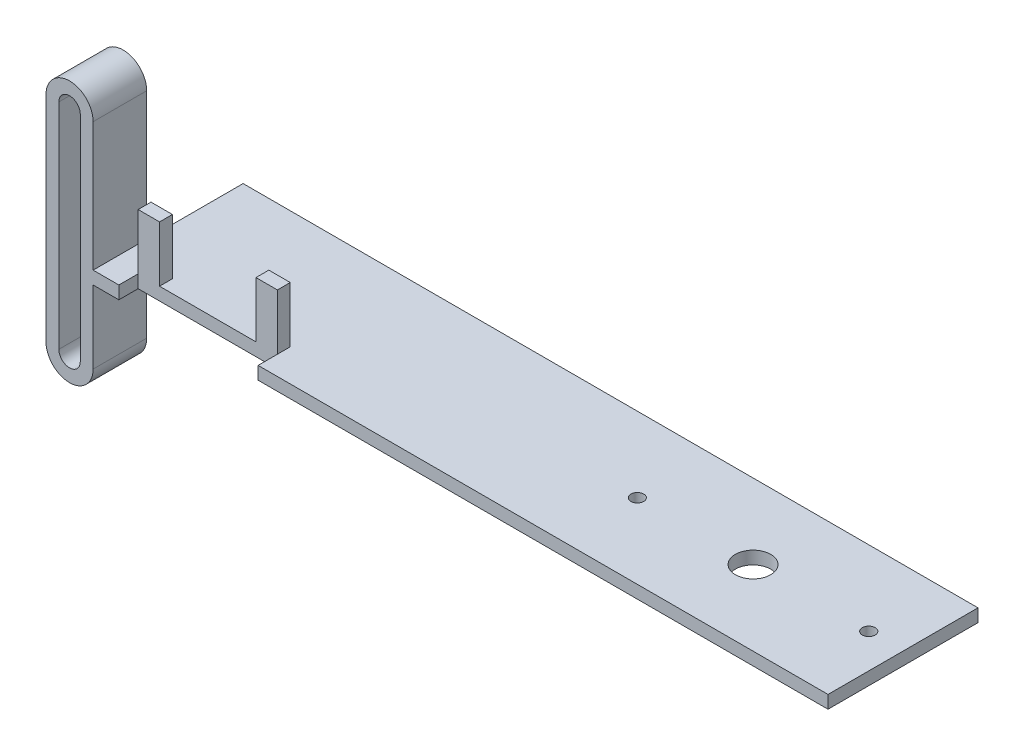
SolidWorks part; units mm, degrees
ref_plane "Front Plane" through (0, 0, 0) normal (0, 0, 1) x (1, 0, 0)
ref_plane "Top Plane" through (0, 0, 0) normal (0, 1, 0) x (1, 0, 0)
ref_plane "Right Plane" through (0, 0, 0) normal (1, 0, 0) x (0, 0, -1)
sketch "Sketch1" plane through (0, 0, 0) normal (0, 1, 0) x (1, 0, 0)
  line L0 (47.5, 13.6856) -> (47.5, -3.2344) construction
  line L1 (-100, 22.5) -> (82.5, 22.5)
  line L2 (-100, 22.5) -> (-100, -12.5)
  line L3 (-100, -12.5) -> (82.5, -12.5)
  line L4 (82.5, 22.5) -> (82.5, -12.5)
  line L6 (12.5, -1) -> (82.5, -1)
  line L7 (12.5, -1) -> (12.5, 11)
  line L8 (12.5, 11) -> (82.5, 11)
  line L9 (82.5, -1) -> (82.5, 11)
  line L10 (12.5, -1) -> (82.5, 11) construction
  line L11 (12.5, 11) -> (82.5, -1) construction
  circle A4 centre (47.5, 5) radius 4.125
  circle A5 centre (74.5, 5) radius 1.5
  circle A6 centre (20.5, 5) radius 1.5
  point P0 (0, 0)
  point P19 (0, 0)
  point P20 (0, 0)
  dimension "D4" = 8.25
  dimension "D5" = 3
  dimension "D1" = 35
  dimension "D2" = 182.5
  dimension "D6" = 8
  dimension "D7" = 70
  dimension "D8" = 12
extrude "Boss-Extrude1" add sketch "Sketch1" along normal blind 3 contours L7 L8 L4 L1 L2 L3 L6 | L8 L7 L6 L4 A4 A5 A6 region at (-17.2674, 0, -5) region at (81.7898, 0, -5)
sketch "Sketch2" plane through (0, 0, 0) normal (0, 0, 1) x (1, 0, 0)
  line L0 (-94.5, 33) -> (-94.5, -17) construction
  line L1 (-92, 33) -> (-92, -17)
  line L2 (-97, 33) -> (-97, -17)
  line L3 (-89, 33) -> (-89, -17)
  line L4 (-100, 33) -> (-100, -17)
  line L7 (-83, 6.4998) -> (-50.5, 6.4998)
  line L8 (-83, 6.4998) -> (-83, -3.3981)
  line L9 (-83, -3.3981) -> (-50.5, -3.3981)
  line L10 (-50.5, 6.4998) -> (-50.5, -3.3981)
  arc A0 (-92, 33) -> (-97, 33) centre (-94.5, 33) ccw
  arc A1 (-97, -17) -> (-92, -17) centre (-94.5, -17) ccw
  arc A2 (-100, -17) -> (-89, -17) centre (-94.5, -17) ccw
  arc A3 (-89, 33) -> (-100, 33) centre (-94.5, 33) ccw
  point P2 (-94.5, 8)
  dimension "D4" = 5.5
  dimension "D1" = 3
  dimension "D2" = 3
  dimension "D3" = 5
  dimension "D5" = 50
  dimension "D6" = 50
  dimension "D7" = 6
  dimension "D8" = 32.5
extrude "Boss-Extrude2" add sketch "Sketch2" along normal up to surface (12.5 mm away) contours L3 A3 L4 A2 A1 L2 A0 L1 region at (-89.6198, 8, 0) up to face at (-8.75, 1.5, 12.5)
extrude "Cut-Extrude1" cut sketch "Sketch2<2>" against normal through all both and the other way through all contours L2 A1 L1 A0 region at (-94.5, 8, 0)
sketch "Sketch2<2>" plane through (0, 0, 0) normal (0, 0, 1) x (1, 0, 0) same geometry as "Sketch2"
extrude "Cut-Extrude2" cut sketch "Sketch2<3>" against normal up to surface (22.5 mm away) contours L3 A3 L4 A2 A1 L2 A0 L1 region at (-89.6198, 8, 0) up to face at (-4.75, 1.5, -22.5)
sketch "Sketch2<3>" plane through (0, 0, 0) normal (0, 0, 1) x (1, 0, 0) same geometry as "Sketch2"
extrude "Cut-Extrude3" cut sketch "Sketch2<5>" along normal up to surface (12.5 mm away) from offset 8 contours L10 L7 L8 L9 region at (-66.75, 1.5509, 0) up to face at (-94.5, 8, 12.5)
sketch "Sketch2<5>" plane through (0, 0, 0) normal (0, 0, 1) x (1, 0, 0) same geometry as "Sketch2"
sketch "Sketch4" plane through (0, 0, 8) normal (0, 0, 1) x (1, 0, 0)
  line L1 (-83, 3) -> (-78, 3)
  line L2 (-83, 3) -> (-83, 16)
  line L3 (-83, 16) -> (-78, 16)
  line L4 (-78, 3) -> (-78, 16)
  line L5 (-50.5, 3) -> (-55.5, 3)
  line L6 (-50.5, 3) -> (-50.5, 16)
  line L7 (-50.5, 16) -> (-55.5, 16)
  line L8 (-55.5, 3) -> (-55.5, 16)
extrude "Boss-Extrude3" add sketch "Sketch4" against normal blind 3
